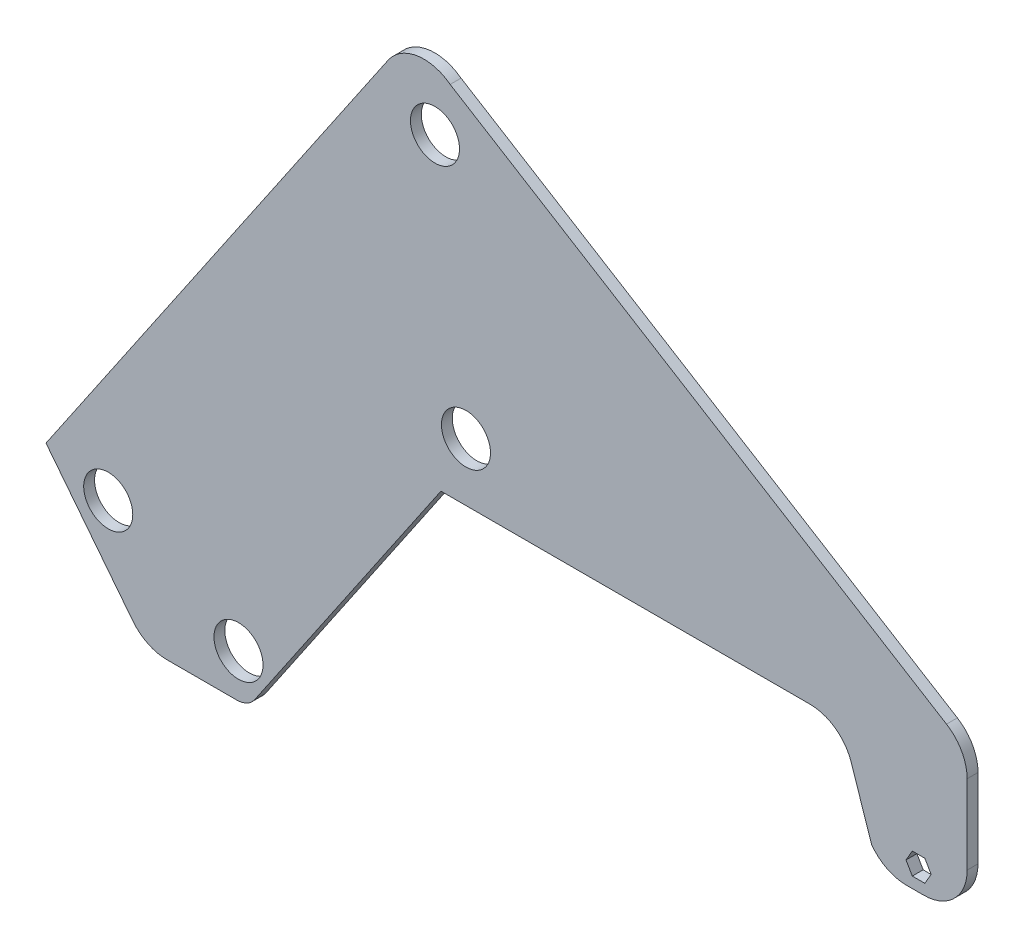
SolidWorks part; units mm, degrees
other "Markup1"
sketch "Sketch1" plane through (-441.7893, 331.8239, 6.35) normal (-0.0431, 0.0102, 0.999) x (0.9985, 0.0354, 0.0427)
sketch "Sketch2" plane through (-413.6701, 343.933, 6.35) normal (-0.0431, 0.0102, 0.999) x (0.9985, 0.0354, 0.0427)
sketch "Sketch3" plane through (-436.3774, 318.5567, 6.35) normal (-0.0431, 0.0102, 0.999) x (0.9985, 0.0354, 0.0427)
other "Markup2"
sketch "Sketch4" plane through (102.4721, 318.5567, 6.35) normal (0.9364, 0.1073, 0.3342) x (0.3416, -0.0598, -0.9379)
ref_plane "Front Plane" through (0, 0, 0) normal (0, 0, 1) x (1, 0, 0)
ref_plane "Top Plane" through (0, 0, 0) normal (0, 1, 0) x (1, 0, 0)
ref_plane "Right Plane" through (0, 0, 0) normal (1, 0, 0) x (0, 0, -1)
sketch "Model" plane through (0, 0, 0) normal (0, 0, 1) x (1, 0, 0)
  line L1 (-205.3388, 104.6502) -> (-2.1388, 104.6502)
  line L3 (-314.2383, -55.3595) -> (-205.3388, 104.6502)
  line L4 (-236.3032, 307.4477) -> (-436.3774, 13.472)
  line L5 (-436.3774, 13.472) -> (-385.5815, -51.2028)
  line L13 (81.3935, 53.8502) -> (77.7274, 60.2002)
  line L14 (77.7274, 60.2002) -> (70.395, 60.2002)
  line L15 (70.395, 60.2002) -> (66.7288, 53.8502)
  line L16 (66.7288, 53.8502) -> (70.395, 47.5002)
  line L17 (70.395, 47.5002) -> (77.7274, 47.5002)
  line L18 (77.7274, 47.5002) -> (81.3935, 53.8502)
  line L19 (-365.606, -60.914) -> (-324.7375, -60.914)
  line L20 (-871.0211, -88.854) -> (370.1019, -88.854) construction
  line L22 (102.4721, 66.5502) -> (102.4721, 83.8724)
  line L27 (67.0531, 41.1502) -> (77.0721, 41.1502)
  line L28 (-399.9752, 2.586) -> (-323.7752, -35.514) construction
  line L29 (-323.7752, -35.514) -> (-190.7071, 138.5169) construction
  line L30 (-190.7071, 138.5169) -> (-208.8329, 283.4378) construction
  line L31 (-208.8329, 283.4378) -> (-399.9752, 2.586) construction
  line L32 (46.5921, 51.5001) -> (34.6564, 87.2866)
  line L33 (10.5612, 104.6502) -> (-11.3966, 104.6502)
  line L34 (102.4721, 83.8724) -> (102.4721, 112.8538)
  line L35 (90.397, 134.478) -> (-199.9496, 313.3896)
  circle A9 centre (-323.7752, -35.514) radius 14.351
  circle A10 centre (-399.9752, 2.586) radius 14.351
  circle A12 centre (-190.7071, 138.5169) radius 14.351
  circle A22 centre (-208.8329, 283.4378) radius 14.351
  circle A24 centre (74.0612, 53.8502) radius 6.35 construction
  arc A31 (-324.7375, -60.914) -> (-314.2383, -55.3595) centre (-324.7375, -48.214) ccw
  arc A40 (46.5921, 51.5001) -> (67.0531, 41.1502) centre (67.0531, 66.5502) ccw
  arc A43 (77.0721, 41.1502) -> (102.4721, 66.5502) centre (77.0721, 66.5502) ccw
  arc A44 (-236.3032, 307.4477) -> (-199.9496, 313.3896) centre (-215.305, 293.1567) cw
  arc A45 (-365.606, -60.914) -> (-385.5815, -51.2028) centre (-365.606, -35.514) cw
  arc A46 (34.6564, 87.2866) -> (10.5612, 104.6502) centre (10.5612, 79.2502) ccw
  arc A47 (102.4721, 112.8538) -> (90.397, 134.478) centre (77.0721, 112.8538) ccw
  point P31 (-221.2548, 329.5588)
  point P34 (100.2935, -12.8222)
  point P43 (-377.9543, -60.914)
  point P59 (174.831, 53.8502)
  dimension "D3" = 38.1
  dimension "D4" = 104.6502
  dimension "D5" = 76.2
  dimension "D6" = 25.4
  dimension "D7" = 12.7
  dimension "D8" = 28.702
  dimension "D11" = 139.7
  dimension "D12" = 27.94
  dimension "D21" = 124.238
  dimension "D13" = 12.7
  dimension "D16" = 355.6
  dimension "D23" = 25.4
  dimension "D24" = 25.4
  dimension "D26" = 25.4
  dimension "D14" = 406.4
  dimension "D20" = 215.9
  dimension "D29" = 25.4
  dimension "D31" = 25.4
  dimension "D25" = 88.9
  dimension "D9" = 19.05
  dimension "D10" = 146.05
  dimension "D15" = 33.8667
  dimension "D17" = 339.725
  dimension "D18" = 219.075
  dimension "D19" = 50.8
  dimension "D22" = 25.4
  dimension "D27" = 53.2168
  dimension "D28" = 12.7
  dimension "D30" = 55.88
extrude "Boss-Extrude1" add sketch "Model" along normal blind 6.35 contours L5 L3 L1 L4 A22 A9 A10 A12 region at (-265.237, 28.3535, 0)
